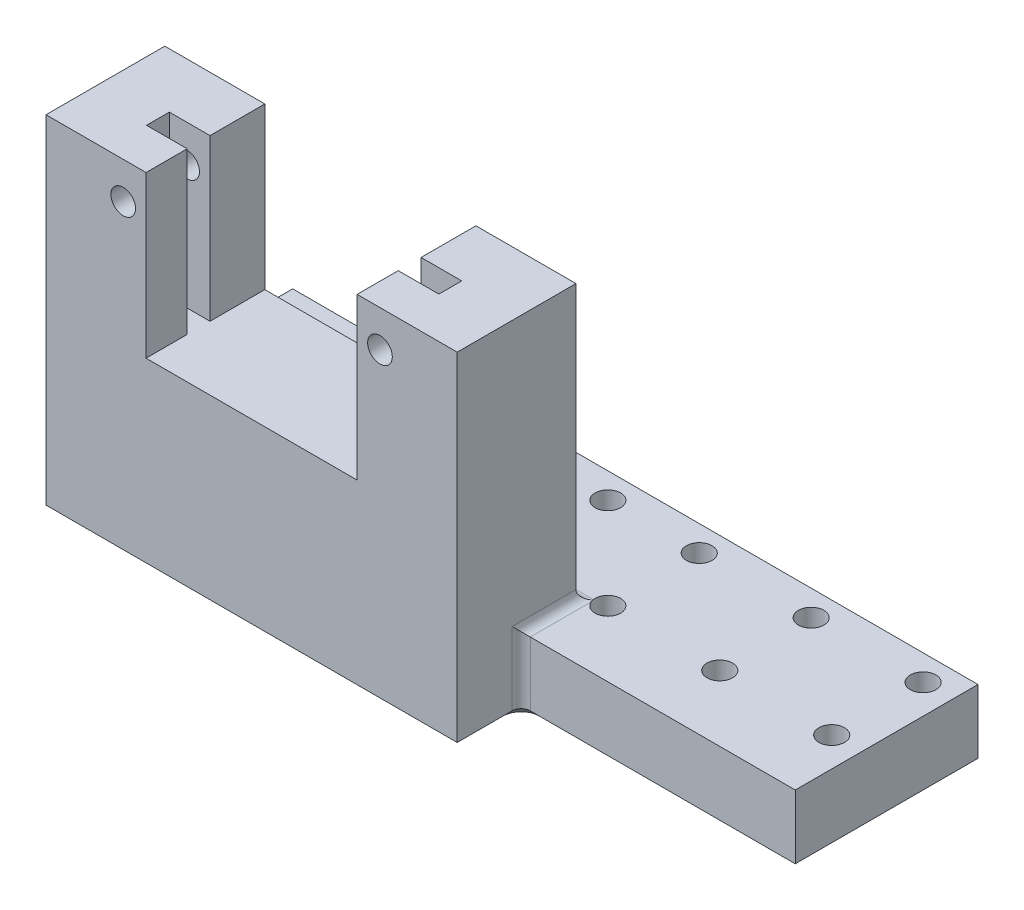
SolidWorks part; units mm, degrees
material "ABS"
ref_plane "Front Plane" through (0, 0, 0) normal (0, 0, 1) x (1, 0, 0)
ref_plane "Top Plane" through (0, 0, 0) normal (0, 1, 0) x (1, 0, 0)
ref_plane "Right Plane" through (0, 0, 0) normal (1, 0, 0) x (0, 0, -1)
sketch "Sketch1" plane through (0, 0, 0) normal (0, 1, 0) x (1, 0, 0)
  line L1 (0, 0) -> (45, 0)
  line L2 (0, 0) -> (0, 6)
  line L3 (0, 6) -> (45, 6)
  line L4 (45, 0) -> (45, 6)
  dimension "D1" = 45
  dimension "D2" = 6
extrude "Boss-Extrude1" add sketch "Sketch1" along normal blind 32
sketch "Sketch2" plane through (0, 0, 0) normal (0, 0, 1) x (1, 0, 0)
  line L0 (0, 32) -> (45, 32) construction
  line L2 (10.95, 32) -> (10.95, 14.4)
  line L3 (10.95, 14.4) -> (34.05, 14.4)
  line L4 (34.05, 32) -> (34.05, 14.4)
  line L5 (10.95, 32) -> (34.05, 32)
  line L6 (22.5, 14.4) -> (22.5, 0) construction
  line L7 (0, 0) -> (45, 0) construction
  dimension "D1" = 23.1
  dimension "D3" = 14.4
extrude "Cut-Extrude1" cut sketch "Sketch2" against normal through all
sketch "Sketch3" plane through (0, 0, 0) normal (0, -1, 0) x (1, 0, 0)
  line L0 (45, 0) -> (45, -6) construction
  line L1 (0, 0) -> (45, 0)
  line L2 (0, 0) -> (0, -20)
  line L3 (0, -20) -> (45, -20)
  line L4 (45, 0) -> (45, -20)
  dimension "D1" = 20
extrude "Boss-Extrude2" add sketch "Sketch3" along normal blind 6
sketch "Sketch4" plane through (45, 0, 0) normal (1, 0, 0) x (0, 0, -1)
  line L1 (20, 0) -> (0, 0)
  line L2 (20, 0) -> (20, -6)
  line L3 (20, -6) -> (0, -6)
  line L4 (0, 0) -> (0, -6)
extrude "Boss-Extrude3" add sketch "Sketch4" along normal blind 30
sketch "Sketch5" plane through (0, -6, 0) normal (0, -1, 0) x (1, 0, 0)
  line L0 (47.2888, -7.2) -> (59.5388, -7.2) construction
  line L1 (37.2888, -17.2) -> (47.2888, -17.2) construction
  line L2 (47.2888, -17.2) -> (59.5388, -17.2) construction
  line L3 (59.5388, -17.2) -> (71.7888, -17.2) construction
  line L4 (71.7888, -17.2) -> (71.7888, -7.2) construction
  line L5 (59.5388, -7.2) -> (59.5388, -17.2) construction
  line L6 (47.2888, -7.2) -> (47.2888, -17.2) construction
  line L7 (0, -20) -> (75, -20) construction
  line L8 (75, 0) -> (75, -20) construction
  line L9 (59.5388, -7.2) -> (71.7888, -7.2) construction
  circle A1 centre (37.2888, -17.2) radius 1.4
  circle A5 centre (47.2888, -17.2) radius 1.4
  circle A7 centre (47.2888, -7.2) radius 1.4
  circle A9 centre (59.5388, -17.2) radius 1.4
  circle A11 centre (71.7888, -17.2) radius 1.4
  circle A13 centre (71.7888, -7.2) radius 1.4
  circle A14 centre (59.5388, -7.2) radius 1.4
  dimension "D1" = 10
  dimension "D2" = 12.25
  dimension "D6" = 2.8
  dimension "D7" = 3.2112
  dimension "D3" = 12.25
  dimension "D4" = 2.8
  dimension "D5" = 10
extrude "Cut-Extrude2" cut sketch "Sketch5" against normal through all
sketch "Sketch6" plane through (0, 0, 0) normal (0, 0, 1) x (1, 0, 0)
  line L0 (0, -6) -> (0, 32)
  line L1 (0, 32) -> (10.95, 32)
  line L2 (10.95, 32) -> (10.95, 14.4)
  line L3 (10.95, 14.4) -> (34.05, 14.4)
  line L4 (34.05, 14.4) -> (34.05, 32)
  line L5 (34.05, 32) -> (45, 32)
  line L6 (45, 32) -> (45, -6)
  line L7 (75, -6) -> (0, -6) construction
  line L8 (45, -6) -> (-0.8534, -6)
  line M1 (45, 32) -> (34.05, 32)
  line M2 (34.05, 32) -> (34.05, 14.4)
  line M3 (34.05, 14.4) -> (10.95, 14.4)
  line M4 (10.95, 14.4) -> (10.95, 32)
  line M5 (10.95, 32) -> (0, 32)
  line M6 (0, 32) -> (0, -6)
  line M7 (0, -6) -> (75, -6)
  line M10 (45, 0) -> (45, 32)
extrude "Boss-Extrude4" add sketch "Sketch6" along normal blind 7 contours L6 M10 M1 M2 M3 M4 M5 M6 M7 region at (22.5, 9.8185, 0)
sketch "Sketch7" plane through (0, 32, 0) normal (0, 1, 0) x (1, 0, 0)
  line L1 (6.5, 0) -> (38.5, 0)
  line L2 (6.5, 0) -> (6.5, -2.5)
  line L3 (6.5, -2.5) -> (38.5, -2.5)
  line L4 (38.5, 0) -> (38.5, -2.5)
  line L5 (22.5, 6) -> (22.5, 0) construction
  line L6 (10.95, 6) -> (34.05, 6) construction
  dimension "D1" = 2.5
  dimension "D2" = 32
extrude "Cut-Extrude3" cut sketch "Sketch7" against normal up to surface (17.6 mm away) up to face at (22.5, 14.4, 0.5)
sketch "Sketch8" plane through (0, 0, 7) normal (0, 0, 1) x (1, 0, 0)
  line L0 (10.95, 32) -> (0, 32) construction
  line L1 (10.95, 14.4) -> (10.95, 32) construction
  line L2 (34.05, 32) -> (34.05, 14.4) construction
  circle A0 centre (8.45, 28) radius 1.35
  circle A1 centre (36.55, 28) radius 1.35
  dimension "D1" = 2.7
  dimension "D3" = 2.5
  dimension "D2" = 4
  dimension "D4" = 2.5
extrude "Cut-Extrude4" cut sketch "Sketch8" against normal through all
sketch "Sketch9" plane through (0, 0, 0) normal (0, 1, 0) x (1, 0, 0)
  line L6 (0, 6) -> (45, 6)
  line L7 (45, 6) -> (45, 0)
  line L8 (45, 0) -> (75, 0)
  line L9 (75, 0) -> (75, 20)
  line L10 (75, 20) -> (0, 20)
  line L11 (0, 20) -> (0, 6)
  line L12 (0, 6) -> (45, 6)
  line L13 (45, 6) -> (45, 0)
  line L14 (45, 0) -> (75, 0)
  line L15 (75, 0) -> (75, 20)
  line L16 (75, 20) -> (0, 20)
  line L17 (0, 20) -> (0, 6)
  circle A0 centre (71.7888, 17.2) radius 1.4 construction
  circle A1 centre (59.5388, 17.2) radius 1.4 construction
  circle A2 centre (71.7888, 7.2) radius 1.4 construction
  circle A3 centre (59.5388, 7.2) radius 1.4 construction
  circle A4 centre (47.2888, 7.2) radius 1.4 construction
  circle A5 centre (47.2888, 17.2) radius 1.4 construction
  circle A6 centre (37.2888, 17.2) radius 1.4 construction
  circle A7 centre (71.7888, 17.2) radius 1.4
  circle A8 centre (59.5388, 17.2) radius 1.4
  circle A9 centre (71.7888, 7.2) radius 1.4
  circle A10 centre (59.5388, 7.2) radius 1.4
  circle A11 centre (47.2888, 7.2) radius 1.4
  circle A12 centre (47.2888, 17.2) radius 1.4
  circle A13 centre (37.2888, 17.2) radius 1.4
  dimension "D1" = 0
extrude "Boss-Extrude5" add sketch "Sketch9" along normal blind 2
fillet "Fillet1" radius 1 3 edges at (45, -2, 0) (45, 2, -3) (22.5, 2, -6)
chamfer "Chamfer1" distance 1 angle 45 7 edges at (0, -6, -6.5) (37.5, -6, -20) (75, -6, -10) (60.5, -6, 0) (45, -6, 4) (22.5, -6, 7) (45.2929, -6, 0.2929)
